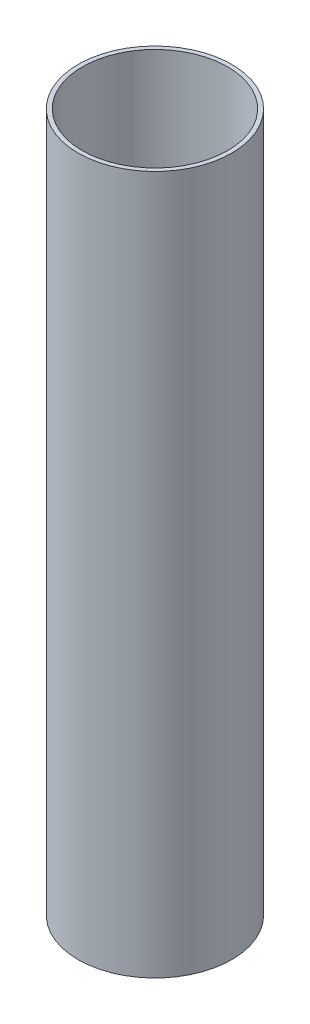
SolidWorks part; units mm, degrees
ref_plane "Спереди" through (0, 0, 0) normal (0, 0, 1) x (1, 0, 0)
ref_plane "Сверху" through (0, 0, 0) normal (0, 1, 0) x (1, 0, 0)
ref_plane "Справа" through (0, 0, 0) normal (1, 0, 0) x (0, 0, -1)
sketch "Эскиз1" plane through (0, 0, 0) normal (0, 1, 0) x (1, 0, 0)
  circle A0 centre (0, 0) radius 55
extrude "Вытянуть-Тонкостенный1" add sketch "Эскиз1" along normal blind 500 thin thin type one direction reverse wall 3
